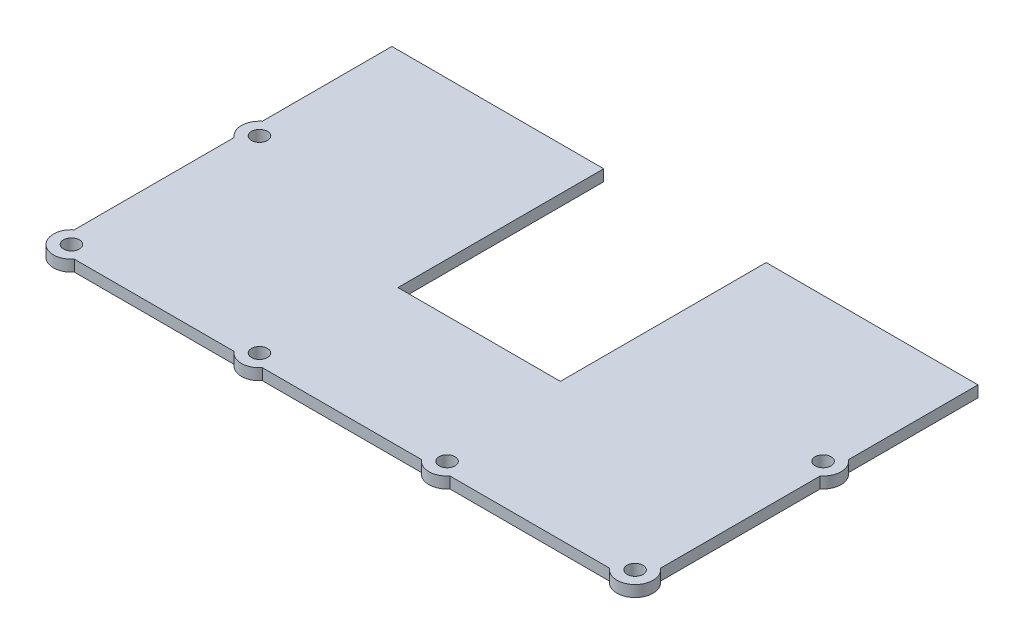
SolidWorks part; units mm, degrees
material "UHMW"
ref_plane "Front Plane" through (0, 0, 0) normal (0, 0, 1) x (1, 0, 0)
ref_plane "Top Plane" through (0, 0, 0) normal (0, 1, 0) x (1, 0, 0)
ref_plane "Right Plane" through (0, 0, 0) normal (1, 0, 0) x (0, 0, -1)
sketch "Sketch1" plane through (0, 0, 0) normal (0, 1, 0) x (1, 0, 0)
  circle A0 centre (3.175, -40.4401) radius 2.2479
  circle A1 centre (3.175, -93.3568) radius 2.2479
  circle A2 centre (56.0917, -93.3568) radius 2.2479
  circle A3 centre (108.8828, -93.3568) radius 2.2479
  circle A4 centre (161.7995, -93.3568) radius 2.2479
  circle A5 centre (161.7995, -40.4401) radius 2.2479
  point P13 (102.5193, -72.8218)
  line B0 (59.6265, 0) -> (0, 0)
  line B1 (59.6265, 0) -> (59.6265, -57.9238)
  line B2 (164.9745, -36.4745) -> (164.9745, 0)
  line B3 (164.9745, -89.3912) -> (164.9745, -44.4057)
  line B4 (112.8484, -96.5318) -> (157.8339, -96.5318)
  line B5 (101.6, -96.5318) -> (104.9173, -96.5318)
  line B6 (101.6, -96.5318) -> (95.25, -96.5318)
  line B7 (69.85, -96.5318) -> (95.25, -96.5318)
  line B8 (69.85, -96.5318) -> (63.5, -96.5318)
  line B9 (60.0572, -96.5318) -> (63.5, -96.5318)
  line B10 (7.1406, -96.5318) -> (52.1261, -96.5318)
  line B11 (0, -44.4057) -> (0, -89.3912)
  line B12 (0, 0) -> (0, -36.4745)
  line B13 (164.9745, 0) -> (105.348, 0)
  line B14 (105.348, 0) -> (105.348, -57.9238)
  line B15 (59.6265, -57.9238) -> (105.348, -57.9238)
  arc B16 (164.9745, -44.4057) -> (164.9745, -36.4745) centre (161.7995, -40.4401) ccw
  arc B17 (157.8339, -96.5318) -> (164.9745, -89.3912) centre (161.7995, -93.3568) ccw
  arc B18 (104.9173, -96.5318) -> (112.8484, -96.5318) centre (108.8828, -93.3568) ccw
  arc B19 (52.1261, -96.5318) -> (60.0572, -96.5318) centre (56.0917, -93.3568) ccw
  arc B20 (0, -89.3912) -> (7.1406, -96.5318) centre (3.175, -93.3568) ccw
  arc B21 (0, -36.4745) -> (0, -44.4057) centre (3.175, -40.4401) ccw
  dimension "D1" = 4.4958
sketch_block_instance "Block-topplate-1"
sketch_block "Block-topplate" parameters "D1"=72.8218, "D2"=72.8218, "D3"=25.4
extrude "Boss-Extrude1" add sketch "Sketch1" along normal blind 3.175
equation "\"Unit Measure\"= \"BoundingVolume\" / \"Thickness\"'in^2"
